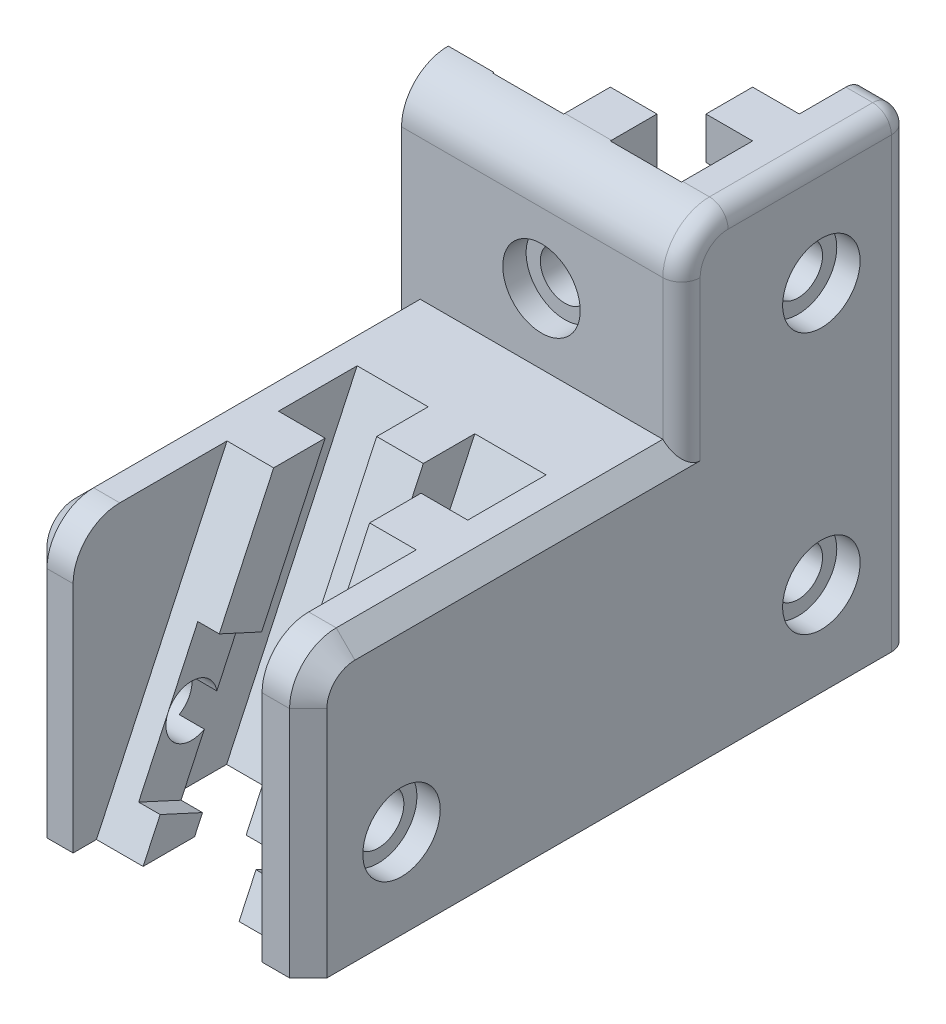
SolidWorks part; units mm, degrees
ref_plane "Front Plane" through (0, 0, 0) normal (0, 0, 1) x (1, 0, 0)
ref_plane "Top Plane" through (0, 0, 0) normal (0, 1, 0) x (1, 0, 0)
ref_plane "Right Plane" through (0, 0, 0) normal (1, 0, 0) x (0, 0, -1)
sketch "Z extrusion mount" plane through (0, 0, 0) normal (0, 1, 0) x (1, 0, 0)
  line L1 (-15, -15) -> (15, -15)
  line L2 (-15, -15) -> (-15, 15)
  line L3 (-15, 15) -> (15, 15)
  line L4 (15, -15) -> (15, 15)
  line L5 (-15, -15) -> (15, 15) construction
  line L6 (-15, 15) -> (15, -15) construction
  point P0 (0, 0)
  dimension "D1" = 30
  dimension "D2" = 30
extrude "Boss-Extrude1" add sketch "Z extrusion mount" along normal blind 50
sketch "Sketch2" plane through (0, 50, 0) normal (0, 1, 0) x (1, 0, 0)
  line L0 (0, 10.125) -> (0, -10.125) construction
  line L1 (-10.125, -10.125) -> (10.125, -10.125)
  line L2 (-10.125, -10.125) -> (-10.125, 10.125)
  line L3 (-10.125, 10.125) -> (10.125, 10.125)
  line L4 (10.125, -10.125) -> (10.125, 10.125)
  line L5 (-10.125, -10.125) -> (10.125, 10.125) construction
  line L6 (-10.125, 10.125) -> (10.125, -10.125) construction
  line L7 (-10.125, 0) -> (10.125, 0) construction
  line L8 (0, -10.125) -> (-2.5, -10.125)
  line L9 (-2.5, -10.125) -> (-2.5, -5.125)
  line L10 (-2.5, -5.125) -> (2.5, -5.125)
  line L11 (2.5, -5.125) -> (2.5, -10.125)
  line L12 (10.125, 2.5) -> (5.125, 2.5)
  line L13 (5.125, 2.5) -> (5.125, -2.5)
  line L14 (5.125, -2.5) -> (10.125, -2.5)
  point P0 (0, 0)
  dimension "D1" = 20.25
  dimension "D2" = 20.25
  dimension "D3" = 5
  dimension "D4" = 5
  dimension "D5" = 2.5
  dimension "D6" = 2.5
  dimension "D7" = 5
  dimension "D8" = 5
extrude "Cut-Extrude1" cut sketch "Sketch2" against normal blind 50 contours L10 L11 L1 L4 L3 L2 L9 region at (-0.5294, 50, -0.5294)
sketch "Sketch3" plane through (0, 50, 0) normal (0, 1, 0) x (1, 0, 0)
  line L0 (15, -15) -> (15, 15) construction
  line L1 (-15, 15) -> (15, 15)
  line L2 (-15, 15) -> (-15, 9.4943)
  line L3 (-15, 9.4943) -> (15, 9.4943)
  line L4 (15, 15) -> (15, 9.4943)
extrude "Cut-Extrude3" cut sketch "Sketch3" against normal blind 50
sketch "Sketch4" plane through (0, 0, 15) normal (0, 0, 1) x (1, 0, 0)
  line L0 (15, 50) -> (15, 0) construction
  line L1 (-15, 0) -> (15, 0)
  line L2 (-15, 0) -> (-15, 30)
  line L3 (-15, 30) -> (15, 30)
  line L4 (15, 0) -> (15, 30)
  line L5 (-15, 0) -> (15, 30) construction
  line L6 (-15, 30) -> (15, 0) construction
  point P0 (0, 15)
  dimension "D1" = 30
extrude "Boss-Extrude3" add sketch "Sketch4" along normal blind 40
sketch "Sketch11" plane through (-15, 0, 0) normal (-1, 0, 0) x (0, 0, 1)
  line L0 (35, 30) -> (55, -12.8901) construction
  line L1 (55, 30) -> (15, 30) construction
  line L2 (55, 30) -> (55, 0) construction
  line L3 (45, 8.5549) -> (45, 9.5549) construction
  circle A0 centre (45, 9.5549) radius 2.75
  dimension "D2" = 5.5
  dimension "D1" = 65
  dimension "D3" = 1
ref_plane "45 Angle Plane" through (-15, 30, 35) normal (0, 0.9063, -0.4226) x (-1, 0, 0)
sketch "Sketch12" plane through (-15, 30, 35) normal (0, 0.9063, -0.4226) x (-1, 0, 0)
  line L0 (-14.9267, 10.7882) -> (-14.9267, -9.4618) construction
  line L1 (-25.0517, -9.4618) -> (-4.8017, -9.4618)
  line L2 (-25.0517, -9.4618) -> (-25.0517, 10.7882)
  line L3 (-25.0517, 10.7882) -> (-4.8017, 10.7882)
  line L4 (-4.8017, -9.4618) -> (-4.8017, 10.7882)
  line L5 (-25.0517, -9.4618) -> (-4.8017, 10.7882) construction
  line L6 (-25.0517, 10.7882) -> (-4.8017, -9.4618) construction
  line L7 (-25.3, 0.6632) -> (-4.8017, 0.6632) construction
  line L8 (-14.9267, 10.7882) -> (-17.4408, 10.7882)
  line L9 (-17.4408, 10.7882) -> (-17.4408, 5.7882)
  line L10 (-17.4408, 5.7882) -> (-12.4408, 5.7882)
  line L11 (-12.4408, 5.7882) -> (-12.4408, 10.7882)
  line L12 (-14.9267, 11.0365) -> (-14.9267, -9.4618) construction
  line L13 (-4.8017, 3.1773) -> (-9.8017, 3.1773)
  line L14 (-9.8017, 3.1773) -> (-9.8017, -1.8227)
  line L15 (-9.8017, -1.8227) -> (-4.8017, -1.8227)
  line L16 (-4.5534, 0.6632) -> (-25.0517, 0.6632) construction
  line L17 (-12.4126, -9.4618) -> (-12.4126, -4.4618)
  line L18 (-12.4126, -4.4618) -> (-17.4126, -4.4618)
  line L19 (-17.4126, -4.4618) -> (-17.4126, -9.4618)
  line L20 (-14.9267, -9.7101) -> (-14.9267, 10.7882) construction
  line L21 (-25.0517, -1.851) -> (-20.0517, -1.851)
  line L22 (-20.0517, -1.851) -> (-20.0517, 3.149)
  line L23 (-20.0517, 3.149) -> (-25.0517, 3.149)
  point P0 (-14.9267, 0.6632)
  point P34 (-14.9267, 0.6632)
  dimension "D1" = 20.25
  dimension "D2" = 20.25
  dimension "D3" = 5
  dimension "D4" = 5
  dimension "D5" = 4
extrude "Cut-Extrude4" cut sketch "Sketch12" against normal through all and the other way blind 10 contours L23 L22 L21 L2 L1 L19 L18 L17 L4 L15 L14 L13 L3 L11 L10 L9 region at (-0.0733, 30.2803, 35.601)
fillet "Fillet1" radius 5 1 edges at (0, 30, 55)
fillet "Fillet2" radius 5 1 edges at (0, 50, 15)
extrude "Cut-Extrude14" cut sketch "Sketch11" against normal blind 30
sketch "Sketch22" plane through (15, 0, 0) normal (1, 0, 0) x (0, 0, -1)
  circle A0 centre (-45, 9.5549) radius 4.15
  dimension "D1" = 8.3
extrude "Cut-Extrude17" cut sketch "Sketch22" against normal blind 2.5
sketch "Sketch23" plane through (-15, 0, 0) normal (-1, 0, 0) x (0, 0, 1)
  circle A0 centre (45, 9.5549) radius 4.15
  dimension "D1" = 8.3
extrude "Cut-Extrude18" cut sketch "Sketch23" against normal blind 2.5
fillet "Fillet4" radius 2 3 edges at (15, 50, 0.2528) (15, 48.5355, 13.5355)
sketch "Sketch24" plane through (0, 50, 0) normal (0, 1, 0) x (1, 0, 0)
  line L2 (-15, -10) -> (-10.125, -10)
  line L3 (-15, -10) -> (-15, 9.4943)
  line L4 (-15, 9.4943) -> (-10.125, 9.4943)
  line L5 (-10.125, -10) -> (-10.125, 9.4943)
extrude "Cut-Extrude19" cut sketch "Sketch24" against normal through all
sketch "Sketch25" plane through (15, 0, 0) normal (1, 0, 0) x (0, 0, -1)
  line L0 (9.4943, 0) -> (9.4943, 48) construction
  line L1 (9.4943, 48) -> (-10, 48) construction
  line L2 (-55, 0) -> (9.4943, 0) construction
  circle A0 centre (-0.0057, 38) radius 2.625
  circle A1 centre (-0.0057, 10) radius 2.625
  dimension "D1" = 5.25
  dimension "D2" = 5.25
  dimension "D5" = 9.5
  dimension "D6" = 9.5
  dimension "D3" = 10
  dimension "D4" = 10
extrude "Cut-Extrude20" cut sketch "Sketch25" against normal through all
sketch "Sketch26" plane through (15, 0, 0) normal (1, 0, 0) x (0, 0, -1)
  circle A0 centre (-0.0057, 38) radius 4.15
  circle A1 centre (-0.0057, 10) radius 4.15
  dimension "D1" = 8.3
  dimension "D2" = 8.3
extrude "Cut-Extrude21" cut sketch "Sketch26" against normal blind 2.5
sketch "Sketch27" plane through (0, 0, 15) normal (0, 0, 1) x (1, 0, 0)
  line L0 (0, 45) -> (0, 37.5) construction
  line L1 (13, 45) -> (-15, 45) construction
  circle A0 centre (0, 37.5) radius 2.625
  dimension "D2" = 5.25
  dimension "D1" = 7.5
extrude "Cut-Extrude23" cut sketch "Sketch27" against normal through all
sketch "Sketch28" plane through (0, 0, 15) normal (0, 0, 1) x (1, 0, 0)
  circle A0 centre (0, 37.5) radius 4.15
  dimension "D1" = 8.3
extrude "Cut-Extrude24" cut sketch "Sketch28" against normal blind 2.5
sketch "Sketch29" plane through (0, 0, 5.125) normal (0, 0, -1) x (-1, 0, 0)
  line L1 (-5, 30) -> (5, 30)
  line L2 (-5, 30) -> (-5, 45)
  line L3 (-5, 45) -> (5, 45)
  line L4 (5, 30) -> (5, 45)
  line L5 (-5, 30) -> (5, 45) construction
  line L6 (-5, 45) -> (5, 30) construction
  point P0 (0, 37.5)
  dimension "D1" = 10
  dimension "D2" = 15
extrude "Cut-Extrude25" cut sketch "Sketch29" against normal blind 3
sketch "Sketch31" plane through (5.125, 0, 0) normal (-1, 0, 0) x (0, 0, 1)
  line L1 (-4.9943, 30.5) -> (5.0057, 30.5)
  line L2 (-4.9943, 30.5) -> (-4.9943, 45.5)
  line L3 (-4.9943, 45.5) -> (5.0057, 45.5)
  line L4 (5.0057, 30.5) -> (5.0057, 45.5)
  line L5 (-4.9943, 30.5) -> (5.0057, 45.5) construction
  line L6 (-4.9943, 45.5) -> (5.0057, 30.5) construction
  line L7 (-4.9943, 2.5) -> (5.0057, 2.5)
  line L8 (-4.9943, 2.5) -> (-4.9943, 17.5)
  line L9 (-4.9943, 17.5) -> (5.0057, 17.5)
  line L10 (5.0057, 2.5) -> (5.0057, 17.5)
  line L11 (-4.9943, 2.5) -> (5.0057, 17.5) construction
  line L12 (-4.9943, 17.5) -> (5.0057, 2.5) construction
  point P0 (0.0057, 38)
  point P6 (0.0057, 10)
  dimension "D1" = 15
  dimension "D2" = 10
  dimension "D3" = 15
  dimension "D4" = 10
extrude "Cut-Extrude27" cut sketch "Sketch31" against normal blind 3
sketch "Sketch33" plane through (-15, 30, 35) normal (0, 0.9063, -0.4226) x (-1, 0, 0)
  line L0 (0, 16.4815) -> (-30, 16.4815) construction
  line L1 (-25.0517, 16.4815) -> (-4.8017, 16.4815)
  line L2 (-25.0517, 16.4815) -> (-25.0517, 5.6981)
  line L3 (-25.0517, 5.6981) -> (-4.8017, 5.6981)
  line L4 (-4.8017, 16.4815) -> (-4.8017, 5.6981)
  line L5 (-4.8017, 3.1773) -> (-4.8017, 10.7882) construction
extrude "Cut-Extrude29" cut sketch "Sketch33" against normal through all
sketch "Sketch35" plane through (0, 0, 0) normal (1, 0, 0) x (0, 0, -1)
  line L0 (-45, 9.5549) -> (-35.3755, 30.4885) construction
  line L1 (-37.7474, 14.4752) -> (-45.0337, 17.8251)
  line L2 (-37.7474, 14.4752) -> (-44.9663, 1.2847)
  line L3 (-45.0337, 17.8251) -> (-52.2526, 4.6347)
  line L4 (-44.9663, 1.2847) -> (-52.2526, 4.6347)
  dimension "D1" = 15
  dimension "D2" = 7.5
  dimension "D3" = 8
  dimension "D4" = 4
extrude "Cut-Extrude30" cut sketch "Sketch35" against normal mid plane 15
chamfer "Chamfer1" distance 2 angle 45 6 edges at (15, 12.5, 55) (15, 28.5355, 53.5355) (-15, 12.5, 55) (-15, 28.5355, 53.5355)
fillet "Fillet5" radius 2 3 edges at (11.5625, 50, -9.4943) (14.4142, 49.4142, -9.4943) (15, 24, -9.4943)
